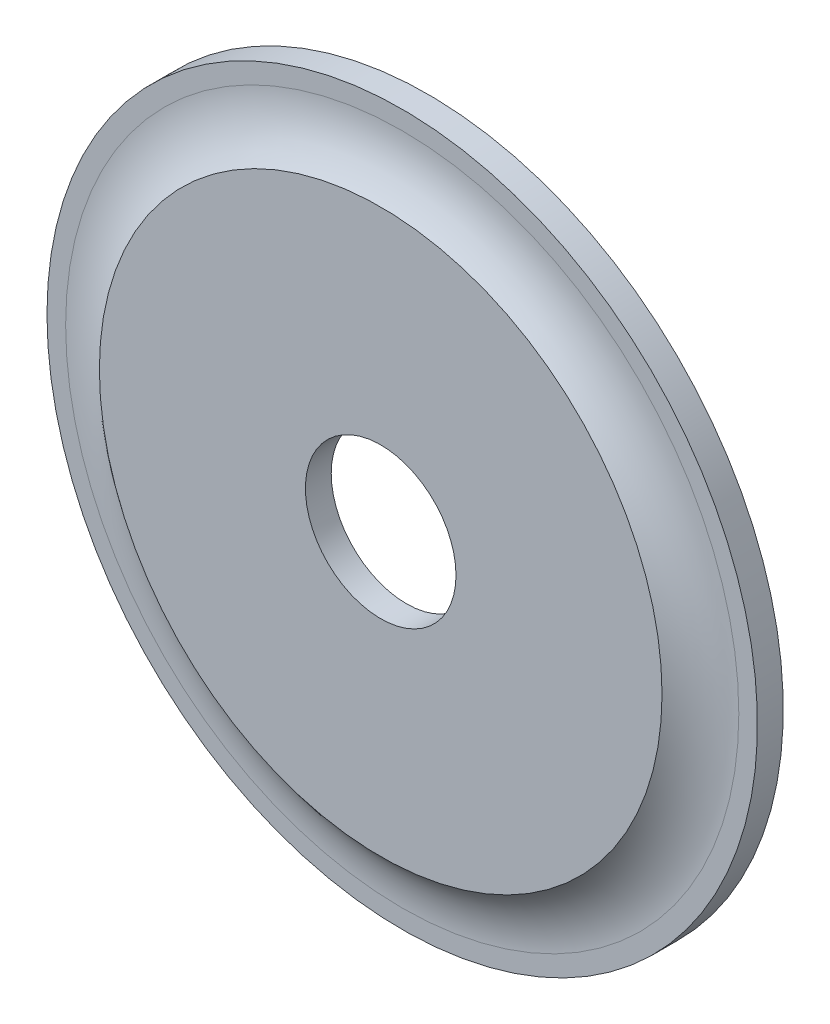
SolidWorks part; units mm, degrees
ref_plane "Front Plane" through (0, 0, 0) normal (0, 0, 1) x (1, 0, 0)
ref_plane "Top Plane" through (0, 0, 0) normal (0, 1, 0) x (1, 0, 0)
ref_plane "Right Plane" through (0, 0, 0) normal (1, 0, 0) x (0, 0, -1)
sketch "Sketch1" plane through (0, 0, 0) normal (0, 0, 1) x (1, 0, 0)
  circle A0 centre (0, 0) radius 0.875
  circle A1 centre (0, 0) radius 3.25
  dimension "D1" = 1.75
  dimension "D2" = 6.5
extrude "Boss-Extrude1" add sketch "Sketch1" along normal blind 0.25
sketch "Sketch2" plane through (0, 0, 0) normal (0, 0, -1) x (-1, 0, 0)
  circle A0 centre (0, 0) radius 4.0783
extrude "Boss-Extrude2" add sketch "Sketch2" along normal blind 0.25
fillet "Fillet1" radius 1 1 edges at (3.25, 0, 0)
shell "Shell1" thickness 0.05 removed face at (-4.0783, 0, -0.25) outward yes
sketch "Sketch3" plane through (0, 0, 0.3) normal (0, 0, 1) x (1, 0, 0)
  circle A2 centre (0, 0) radius 0.875
  dimension "D1" = 1.75
extrude "Cut-Extrude1" cut sketch "Sketch3" against normal blind 2.25
sketch "Sketch4" plane through (0, 0, 0.25) normal (0, 0, -1) x (-1, 0, 0)
  circle A0 centre (0, 0) radius 0.875 construction
  circle A1 centre (0, 0) radius 0.875
  circle A3 centre (0, 0) radius 1.2134
extrude "Boss-Extrude3" add sketch "Sketch4" along normal blind 0.25
chamfer "Chamfer1" distance 0.2 angle 45 1 edges at (-1.2134, 0, 0)
